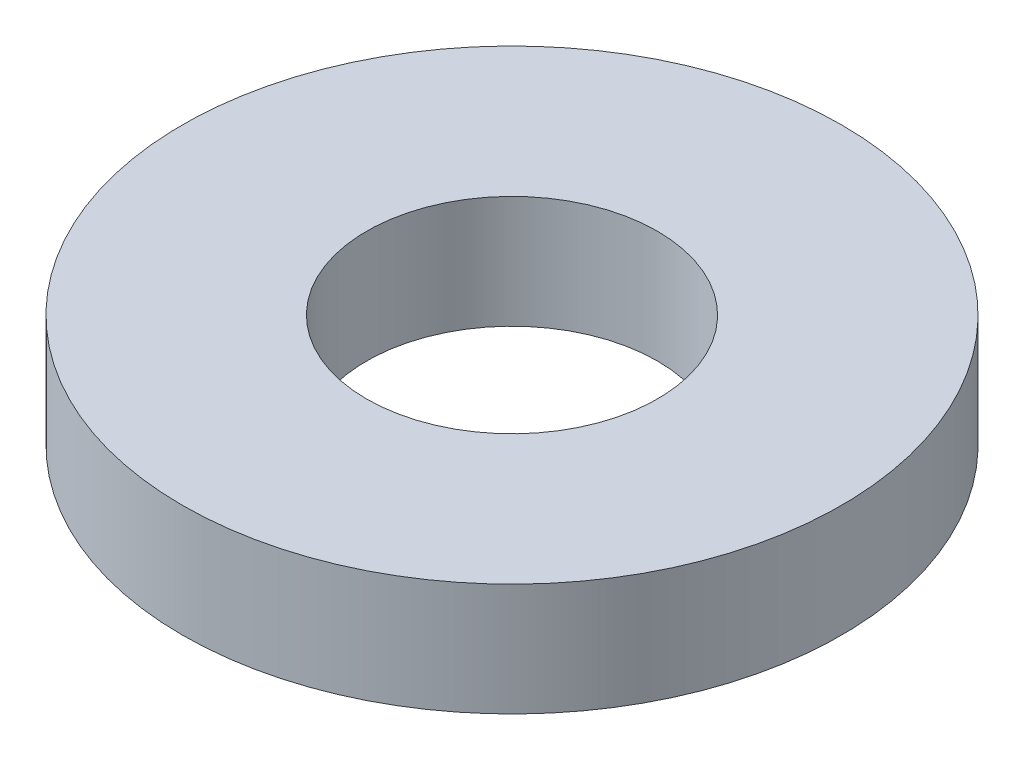
SolidWorks part; units mm, degrees
ref_plane "Front Plane" through (0, 0, 0) normal (0, 0, 1) x (1, 0, 0)
ref_plane "Top Plane" through (0, 0, 0) normal (0, 1, 0) x (1, 0, 0)
ref_plane "Right Plane" through (0, 0, 0) normal (1, 0, 0) x (0, 0, -1)
sketch "Sketch1" plane through (0, 0, 0) normal (0, 1, 0) x (1, 0, 0)
  circle A0 centre (0, 0) radius 85
  dimension "FLANGE_OD" = 170
extrude "Boss-Extrude1" add sketch "Sketch1" along normal blind 29
sketch "Sketch2" plane through (0, 0, 0) normal (0, 1, 0) x (1, 0, 0)
  circle A0 centre (0, 0) radius 37.5
  dimension "BORE_D" = 75
extrude "Cut-Extrude1" cut sketch "Sketch2" along normal through all
sketch "Sketch3" plane through (0, 29, 0) normal (0, 1, 0) x (1, 0, 0)
  circle A0 centre (0, 0) radius 23.6264 construction
  circle A1 centre (-23.6264, 0) radius 6.1628
  dimension "BOLT_D" = 12.3255
  dimension "BOLT_PCD" = 47.2527
extrude "Cut-Extrude2" cut sketch "Sketch3" against normal blind 27.9011 rebuild error yes
pattern_circular "CirPattern1" count 8 over 360 rebuild error yes
